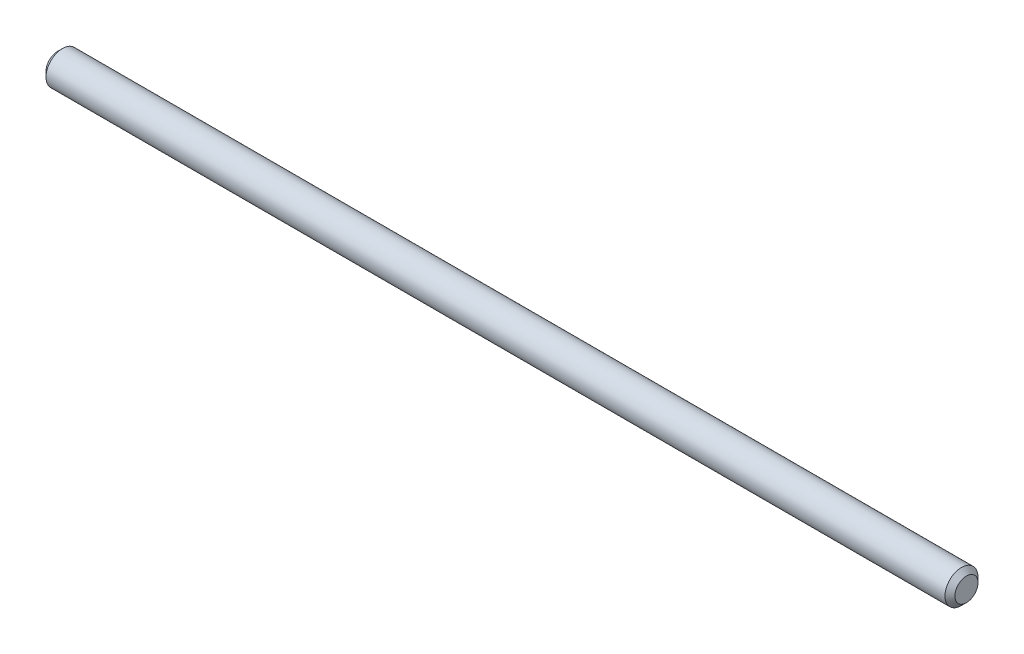
SolidWorks part; units mm, degrees
ref_plane "Front Plane" through (0, 0, 0) normal (0, 0, 1) x (1, 0, 0)
ref_plane "Top Plane" through (0, 0, 0) normal (0, 1, 0) x (1, 0, 0)
ref_plane "Right Plane" through (0, 0, 0) normal (1, 0, 0) x (0, 0, -1)
sketch "Sketch1" plane through (0, 0, 0) normal (0, 0, 1) x (1, 0, 0)
  line L0 (-87.3125, 0) -> (87.3125, 0) construction
  line L1 (87.3125, 3.175) -> (87.3125, -3.175) construction
  line L2 (-87.3125, 3.175) -> (-87.3125, -3.175) construction
  point P6 (82.8675, -3.175)
  dimension "Thread Diameter" = 6.35
  dimension "Length" = 174.625
  dimension "D1" = 4.445
sketch "Sketch2" plane through (0, 0, 0) normal (1, 0, 0) x (0, 0, -1)
  circle A0 centre (0, 0) radius 3.175
extrude "Boss-Extrude1" add sketch "Sketch2" against normal up to vertex (87.3125 mm away) and the other way up to vertex (87.3125 mm away) up to point (-87.3125, 0, 0) other way up to point (87.3125, 0, 0)
cosmetic thread "Cosmetic Thread1" parameters "D2"=4.8387
sketch "Sketch3" plane through (87.3125, 0, 0) normal (1, 0, 0) x (0, 0, -1)
  circle A1 centre (0, 0) radius 3.175
  circle A2 centre (0, 0) radius 3.175
  dimension "D1" = 0
curve "Helix/Spiral1" pitch 1.27 height 175.895 turns 138.5 parameters "Pitch"=1.27
chamfer "Chamfer1" distance 0.9525 angle 45 2 edges at (-87.3125, 0, -3.175) (87.3125, 0, -3.175)
sketch "Sketch4" plane through (0, 0, 0) normal (0, 0, 1) x (1, 0, 0)
  line L0 (87.2331, 3.3125) -> (87.8681, 2.2126) construction
  line L1 (87.8681, 2.2126) -> (88.5031, 3.3125) construction
  line L2 (88.5031, 3.3125) -> (87.2331, 3.3125) construction
  line L3 (87.8681, 3.3125) -> (87.8681, 3.175) construction
  line L4 (87.8681, 2.2126) -> (87.8681, 2.3501) construction
  line L5 (87.7887, 2.3501) -> (87.9475, 2.3501) construction
  line L6 (87.3125, 3.175) -> (88.4237, 3.175) construction
  line L7 (87.7887, 2.3501) -> (87.2728, 3.2437)
  line L8 (87.7887, 2.3501) -> (87.9475, 2.3501)
  line L9 (87.2728, 3.2437) -> (88.4634, 3.2437)
  line L10 (88.4634, 3.2437) -> (87.9475, 2.3501)
  point P13 (87.8681, 3.2437)
  dimension "D2" = 0.1588
sweep "Cut-Sweep3" [suppressed] cut profiles "Sketch4" path "Helix/Spiral1"
equation "\"D3@Helix/Spiral1\" = \"Length@Sketch1\"+\"Pitch@Helix/Spiral1\""
equation "\"D1@Chamfer1\" = \"Pitch@Helix/Spiral1\"*.75"
equation "\"D1@Sketch4\" = \"Pitch@Helix/Spiral1\""
equation "\"D2@Sketch4\" = \"D1@Sketch4\"/8"
equation "\"D1@Sketch1\" = \"Pitch@Helix/Spiral1\"*3.50"
